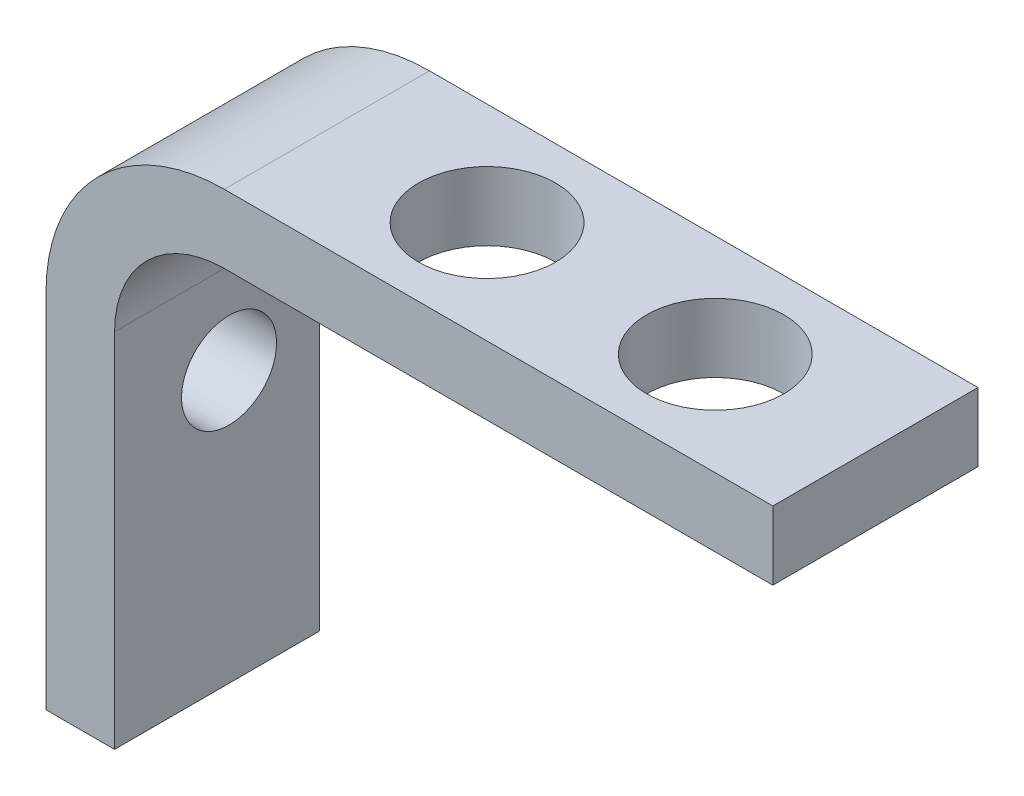
SolidWorks part; units mm, degrees
material "6061 Alloy"
ref_plane "Front Plane" through (0, 0, 0) normal (0, 0, 1) x (1, 0, 0)
ref_plane "Top Plane" through (0, 0, 0) normal (0, 1, 0) x (1, 0, 0)
ref_plane "Right Plane" through (0, 0, 0) normal (1, 0, 0) x (0, 0, -1)
sketch "Sketch1" plane through (0, 0, 0) normal (0, 0, 1) x (1, 0, 0)
  line L0 (0, 0) -> (0, 8.3725)
  line L1 (2.54, 10.9125) -> (15.24, 10.9125)
  line L2 (-1.5875, 0) -> (-1.5875, 8.3725)
  line L3 (2.54, 12.5) -> (15.24, 12.5)
  line L4 (-1.5875, 0) -> (0, 0)
  line L5 (15.24, 10.9125) -> (15.24, 12.5)
  arc A0 (0, 8.3725) -> (2.54, 10.9125) centre (2.54, 8.3725) cw
  arc A1 (-1.5875, 8.3725) -> (2.54, 12.5) centre (2.54, 8.3725) cw
  dimension "D1" = 2.54
  dimension "D2" = 12.7
  dimension "D3" = 12.5
  dimension "D4" = 1.5875
extrude "Boss-Extrude1" add sketch "Sketch1" along normal blind 4.75
sketch "Sketch2" plane through (0, 0, 0) normal (1, 0, 0) x (0, 0, -1)
  line L4 (0, 0) -> (0, 8.3725)
  line L5 (0, 8.3725) -> (-4.75, 8.3725)
  line L6 (-4.75, 8.3725) -> (-4.75, 0)
  line L7 (-4.75, 0) -> (0, 0)
  line L8 (0, 0) -> (0, 8.3725)
  line L9 (0, 8.3725) -> (-4.75, 8.3725)
  line L10 (-4.75, 8.3725) -> (-4.75, 0)
  line L11 (-4.75, 0) -> (0, 0)
  circle A2 centre (-2.1, 6.277) radius 2.0955
  circle A3 centre (-2.1, 6.277) radius 1.1
  dimension "D1" = 0
extrude "Cut-Extrude1" cut sketch "Sketch2" against normal up to next from surface contours A3 region at (0, 6.277, 2.1) starting at face at (0, 4.1863, 2.375)
sketch "Sketch3" plane through (0, 10.9125, 0) normal (0, -1, 0) x (1, 0, 0)
  line L0 (15.24, 2.375) -> (2.54, 2.375) construction
  line L1 (15.24, 4.75) -> (15.24, 0) construction
  line L2 (2.54, 4.75) -> (2.54, 0) construction
  circle A0 centre (6.2484, 2.375) radius 1.5875
  circle A1 centre (11.5316, 2.375) radius 1.5875
  dimension "D1" = 3.7084
  dimension "D3" = 5.2832
  dimension "D2" = 3.7084
extrude "Cut-Extrude2" cut sketch "Sketch3" against normal blind 2.54 contours L0 A0 | L0 A0 | L0 A1 | L0 A1 region at (11.5316, 10.9125, 1.7012) region at (11.5316, 10.9125, 3.0488) region at (6.2484, 10.9125, 1.7012) region at (6.2484, 10.9125, 3.0488)
